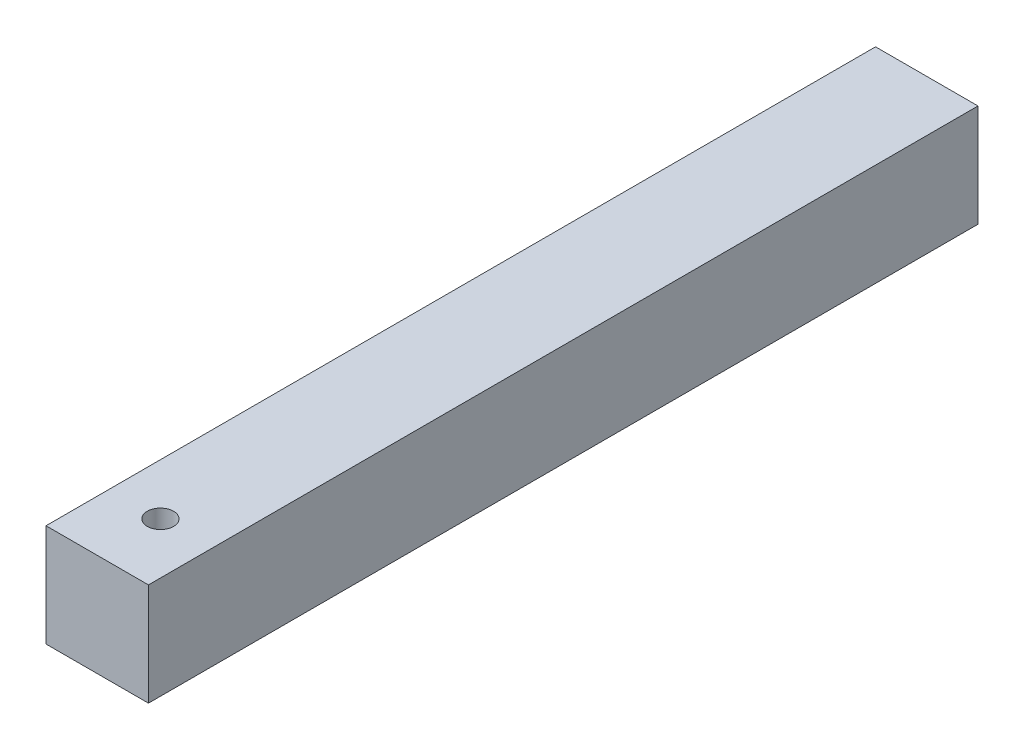
SolidWorks part; units mm, degrees
ref_plane "Front Plane" through (0, 0, 0) normal (0, 0, 1) x (1, 0, 0)
ref_plane "Top Plane" through (0, 0, 0) normal (0, 1, 0) x (1, 0, 0)
ref_plane "Right Plane" through (0, 0, 0) normal (1, 0, 0) x (0, 0, -1)
sketch "Sketch1" plane through (0, 0, 0) normal (0, 0, 1) x (1, 0, 0)
  line L0 (-6.35, -6.35) -> (-6.35, 18.35)
  line L1 (0, 0) -> (12, 0)
  line L2 (0, 0) -> (0, 12)
  line L3 (0, 12) -> (12, 12)
  line L4 (12, 0) -> (12, 12)
  line L5 (-6.35, 18.35) -> (18.35, 18.35)
  line L6 (18.35, -6.35) -> (18.35, 18.35)
  line L7 (-6.35, -6.35) -> (18.35, -6.35)
  dimension "D1" = 12
  dimension "D2" = 6.35
extrude "Boss-Extrude1" add sketch "Sketch1" along normal blind 200 contours L0 L5 L6 L7
extrude "Cut-Extrude1" cut sketch "Sketch1<4>" along normal offset from surface (193.65 mm away) 6.35 contours L4 L3 L2 L1 up to face at (6, 6, 200)
sketch "Sketch1<4>" plane through (0, 0, 0) normal (0, 0, 1) x (1, 0, 0) same geometry as "Sketch1"
sketch "Sketch2" plane through (0, 18.35, 0) normal (0, 1, 0) x (1, 0, 0)
  line L0 (6, -184.76) -> (-6.35, -200) construction
  line L1 (6, -184.76) -> (18.35, -200) construction
  circle A0 centre (6, -184.76) radius 3.175
  dimension "D1" = 6.35
  dimension "D2" = 15.24
extrude "Cut-Extrude2" cut sketch "Sketch2" against normal through all
